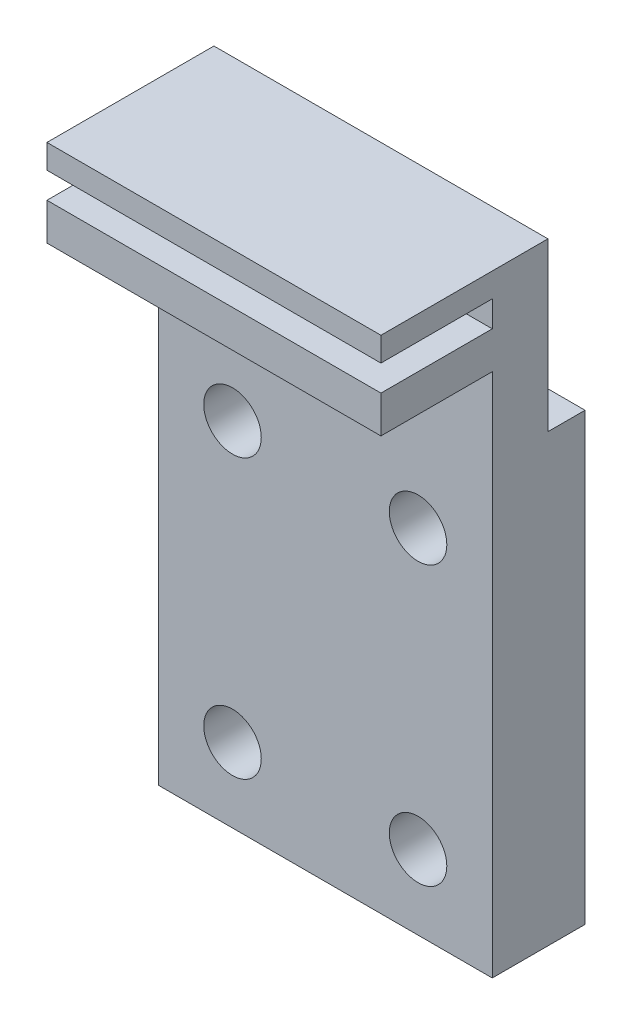
SolidWorks part; units mm, degrees
ref_plane "Ebene vorne" through (0, 0, 0) normal (0, 0, 1) x (1, 0, 0)
ref_plane "Ebene oben" through (0, 0, 0) normal (0, 1, 0) x (1, 0, 0)
ref_plane "Ebene rechts" through (0, 0, 0) normal (1, 0, 0) x (0, 0, -1)
sketch "Skizze1" plane through (0, 0, 0) normal (0, 0, 1) x (1, 0, 0)
  line L0 (10.3603, 19.5) -> (-9.5856, 19.5) construction
  line L1 (-5, 7.5) -> (5, 7.5) construction
  line L2 (-5, 7.5) -> (-5, -7.5) construction
  line L3 (-5, -7.5) -> (5, -7.5) construction
  line L4 (5, 7.5) -> (5, -7.5) construction
  line L5 (-9, 18.8) -> (9, 18.8)
  line L6 (-9, -11.5) -> (9, -11.5)
  line L7 (-9, -11.5) -> (-9, 21.5)
  line L8 (-9, 21.5) -> (9, 21.5)
  line L9 (9, -11.5) -> (9, 21.5)
  line L10 (-9, 20.2) -> (9, 20.2)
  line L11 (-9, 16.8) -> (9, 16.8)
  circle A0 centre (-5, 7.5) radius 1.55
  circle A1 centre (5, 7.5) radius 1.55
  circle A2 centre (5, -7.5) radius 1.55
  circle A3 centre (-5, -7.5) radius 1.55
  point P4 (0, 7.5)
  point P6 (5, 0)
  point P17 (0, -11.5)
  dimension "D3" = 3.1
  dimension "D1" = 10
  dimension "D2" = 15
  dimension "D4" = 12
  dimension "D5" = 4
  dimension "D6" = 4
  dimension "D7" = 2
  dimension "D8" = 0.7
  dimension "D9" = 0.7
  dimension "D10" = 2
extrude "Aufsatz-Linear austragen3" add sketch "Skizze1" against normal blind 5 contours L7 L10 L9 L8 | L10 L7 L5 L9 | L7 L11 L9 L5 | L11 L7 L6 L9 A3 A2 A1 A0 region at (0, 19.5, 0) region at (0, 17.8, 0) region at (0, 2.817, 0) region at (0, 20.85, 0)
extrude "Aufsatz-Linear austragen4" add sketch "Skizze1<4>" along normal blind 6 contours L7 L10 L9 L8 | L7 L11 L9 L5 region at (0, 17.8, 0) region at (0, 20.85, 0)
sketch "Skizze1<4>" plane through (0, 0, 0) normal (0, 0, 1) x (1, 0, 0) same geometry as "Skizze1"
sketch "Skizze2" plane through (9, 0, 0) normal (1, 0, 0) x (0, 0, -1)
  line L6 (5, 21.5) -> (3, 21.5)
  line L7 (5, 21.5) -> (5, 12.5)
  line L8 (5, 12.5) -> (3, 12.5)
  line L9 (3, 21.5) -> (3, 12.5)
  dimension "D1" = 2
  dimension "D2" = 9
extrude "Schnitt-Linear austragen1" cut sketch "Skizze2" against normal through all
